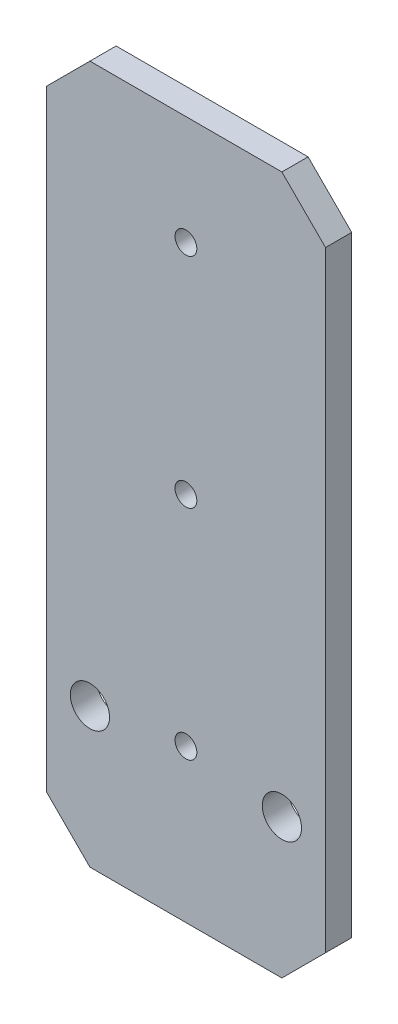
SolidWorks part; units mm, degrees
ref_plane "Front" through (0, 0, 0) normal (0, 0, 1) x (1, 0, 0)
ref_plane "Top" through (0, 0, 0) normal (0, 1, 0) x (1, 0, 0)
ref_plane "Right" through (0, 0, 0) normal (1, 0, 0) x (0, 0, -1)
sketch "Esquisse1" plane through (0, 0, 0) normal (0, 0, 1) x (1, 0, 0)
  line L1 (0, 0) -> (32, 0)
  line L2 (0, 0) -> (0, 80)
  line L3 (0, 80) -> (32, 80)
  line L4 (32, 0) -> (32, 80)
  dimension "D1" = 32
  dimension "D2" = 80
extrude "Boss.-Extru.1" add sketch "Esquisse1" along normal blind 3
sketch "Esquisse2" plane through (0, 0, 3) normal (0, 0, 1) x (1, 0, 0)
  line L0 (16, 0) -> (16, 80) construction
  line L1 (0, 0) -> (32, 0) construction
  line L2 (32, 80) -> (0, 80) construction
  circle A0 centre (16, 17.5) radius 1.25
  circle A1 centre (16, 42.5) radius 1.25
  circle A2 centre (16, 67.5) radius 1.25
  circle A3 centre (16, 92.5) radius 1.25
  circle A4 centre (16, 117.5) radius 1.25
  circle A5 centre (16, 142.5) radius 1.25
  circle A6 centre (16, 167.5) radius 1.25
  circle A7 centre (16, 192.5) radius 1.25
  dimension "D1" = 17.5
  dimension "D2" = 2.5
  dimension "D4" = 25
  dimension "D3" = 8
extrude "Enlèv. mat.-Extru.1" cut sketch "Esquisse2" against normal through all both and the other way through all
sketch "Esquisse3" plane through (0, 0, 3) normal (0, 0, 1) x (1, 0, 0)
  line L0 (16, 0) -> (16, 80) construction
  line L1 (0, 0) -> (32, 0) construction
  line L2 (32, 80) -> (0, 80) construction
  circle A0 centre (5, 16) radius 2.25
  circle A1 centre (27, 16) radius 2.25
  dimension "D1" = 22
  dimension "D2" = 16
  dimension "D3" = 4.5
extrude "Enlèv. mat.-Extru.2" cut sketch "Esquisse3" against normal through all both and the other way through all
chamfer "Chanfrein1" distance 5 angle 45 4 edges at (32, 0, 1.5) (0, 0, 1.5) (32, 80, 1.5) (0, 80, 1.5)
